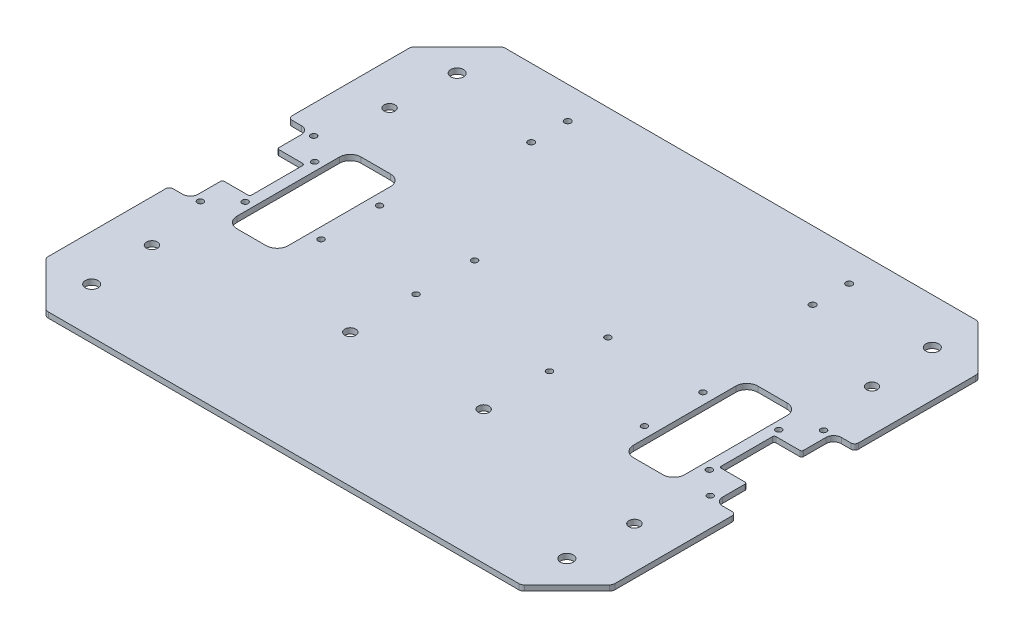
SolidWorks part; units mm, degrees
ref_plane "Plan de face" through (0, 0, 0) normal (0, 0, 1) x (1, 0, 0)
ref_plane "Plan de dessus" through (0, 0, 0) normal (0, 1, 0) x (1, 0, 0)
ref_plane "Plan de droite" through (0, 0, 0) normal (1, 0, 0) x (0, 0, -1)
sketch "Esquisse1" plane through (0, 0, 0) normal (0, 1, 0) x (1, 0, 0)
  line L0 (0, 125) -> (0, -125) construction
  line L1 (-155, 0) -> (155, 0) construction
  line L2 (-130, 125) -> (130, 125)
  line L3 (-130, -125) -> (130, -125)
  line L4 (-155, 100) -> (-155, -100)
  line L5 (155, 100) -> (155, -100)
  line L6 (-155, 100) -> (-130, 125)
  line L7 (-155, -100) -> (-130, -125)
  line L8 (130, -125) -> (155, -100)
  line L9 (130, 125) -> (155, 100)
  point P4 (0, 0)
  point P8 (0, 0)
  point P10 (0, 125)
  point P14 (0, -125)
  point P17 (-155, 0)
  point P20 (155, 0)
  dimension "D1" = 310
  dimension "D2" = 250
  dimension "D3" = 135
  dimension "D4" = 260
  dimension "D5" = 200
extrude "Boss.-Extru.1" add sketch "Esquisse1" along normal blind 3
fillet "Congé1" radius 3 8 edges at (-155, 1.5, 100) (-130, 1.5, 125) (130, 1.5, 125) (155, 1.5, 100) (155, 1.5, -100) (130, 1.5, -125) (-130, 1.5, -125) (-155, 1.5, -100)
sketch "Esquisse2" plane through (0, 3, 0) normal (0, 1, 0) x (1, 0, 0)
  line L0 (155, 0) -> (-155, 0) construction
  line L1 (-155, 98.7574) -> (-155, -98.7574) construction
  line L2 (-132, 0) -> (-132, -65) construction
  line L3 (-132, -65) -> (-155, -65) construction
  line L4 (0, 125) -> (0, -125) construction
  line L5 (-128.7574, -125) -> (128.7574, -125) construction
  circle A0 centre (-132, -65) radius 3
  circle A1 centre (-132, 65) radius 3
  circle A2 centre (132, -65) radius 3
  circle A3 centre (132, 65) radius 3
  point P6 (0, 0)
  point P18 (0, 0)
  dimension "D3" = 6
  dimension "D1" = 23
  dimension "D2" = 65
extrude "Perçage Profilé" cut sketch "Esquisse2" against normal through all
sketch "Esquisse3" plane through (0, 3, 0) normal (0, 1, 0) x (1, 0, 0)
  line L0 (-127, 19) -> (-127, -19) construction
  line L1 (155, 0) -> (-155, 0) construction
  line L2 (-155, 98.7574) -> (-155, -98.7574) construction
  line L3 (0, 125) -> (0, -125) construction
  line L4 (-128.7574, -125) -> (128.7574, -125) construction
  line L5 (-139.5, -31) -> (-139.5, 31) construction
  circle A0 centre (-127, 19) radius 1.65
  circle A1 centre (-127, -19) radius 1.65
  circle A2 centre (127, -19) radius 1.65
  circle A3 centre (127, 19) radius 1.65
  circle A4 centre (-139.5, 31) radius 1.65
  circle A5 centre (-139.5, -31) radius 1.65
  circle A6 centre (139.5, -31) radius 1.65
  circle A7 centre (139.5, 31) radius 1.65
  point P4 (-127, 0)
  point P10 (0, 0)
  point P16 (0, 0)
  point P23 (-139.5, 0)
  dimension "D2" = 3.3
  dimension "D1" = 38
  dimension "D3" = 28
  dimension "D4" = 62
  dimension "D5" = 12.5
extrude "Perçage Encodeur" cut sketch "Esquisse3" against normal through all
sketch "Esquisse4" plane through (0, 3, 0) normal (0, 1, 0) x (1, 0, 0)
  line L0 (155, 0) -> (-155, 0) construction
  line L1 (143.5, -15) -> (129.5, -15)
  line L2 (-128.5, -14) -> (-128.5, 14)
  line L4 (-129.5, 15) -> (-143.5, 15)
  line L5 (-143.5, 15) -> (-143.5, 32.5)
  line L6 (-143.5, 32.5) -> (-152, 32.5)
  line L7 (-152, 32.5) -> (-152, -32.5)
  line L8 (-152, -32.5) -> (-143.5, -32.5)
  line L9 (-143.5, -32.5) -> (-143.5, -15)
  line L10 (-143.5, -15) -> (-129.5, -15)
  line L12 (-143.5, 15) -> (-143.5, -15) construction
  line L13 (143.5, -32.5) -> (143.5, -15)
  line L14 (0, 125) -> (0, -125) construction
  line L15 (-128.7574, -125) -> (128.7574, -125) construction
  line L16 (152, -32.5) -> (143.5, -32.5)
  line L27 (-155, 98.7574) -> (-155, -98.7574) construction
  line L28 (152, 32.5) -> (152, -32.5)
  line L29 (143.5, 32.5) -> (152, 32.5)
  line L30 (143.5, 15) -> (143.5, 32.5)
  line L31 (129.5, 15) -> (143.5, 15)
  line L32 (128.5, -14) -> (128.5, 14)
  arc A0 (-128.5, -14) -> (-129.5, -15) centre (-129.5, -14) cw
  arc A1 (-128.5, 14) -> (-129.5, 15) centre (-129.5, 14) ccw
  arc A2 (128.5, 14) -> (129.5, 15) centre (129.5, 14) cw
  arc A3 (128.5, -14) -> (129.5, -15) centre (129.5, -14) ccw
  point P6 (0, 0)
  point P10 (-128.5, 0)
  point P19 (-143.5, 0)
  point P25 (0, 0)
  point P28 (-128.5, 15)
  point P32 (-152, 0)
  point P45 (128.5, 15)
  point P46 (128.5, 0)
  dimension "D2" = 1
  dimension "D1" = 15
  dimension "D3" = 8.5
  dimension "D4" = 65
  dimension "D5" = 30
  dimension "D6" = 3
extrude "Poche Roue Encodeuse" cut sketch "Esquisse4" against normal through all
fillet "Congé4" radius 1 4 edges at (143.5, 1.5, 15) (143.5, 1.5, -15) (-143.5, 1.5, 15) (-143.5, 1.5, -15)
fillet "Congé2" radius 4.25 4 edges at (152, 1.5, 32.5) (152, 1.5, -32.5) (-152, 1.5, 32.5) (-152, 1.5, -32.5)
fillet "Congé3" radius 4.25 4 edges at (143.5, 1.5, 32.5) (143.5, 1.5, -32.5) (-143.5, 1.5, 32.5) (-143.5, 1.5, -32.5)
sketch "Esquisse5" plane through (0, 3, 0) normal (0, 1, 0) x (1, 0, 0)
  line L0 (0, 125) -> (0, -125) construction
  line L1 (128.7574, 125) -> (-128.7574, 125) construction
  line L2 (-128.7574, -125) -> (128.7574, -125) construction
  line L3 (-155, 0) -> (155, 0) construction
  line L4 (-155, 98.7574) -> (-155, -98.7574) construction
  line L5 (155, -98.7574) -> (155, 98.7574) construction
  line L7 (-36.5, 16) -> (-88.5, 16) construction
  line L8 (-36.5, 16) -> (-36.5, -16) construction
  line L9 (-36.5, -16) -> (-88.5, -16) construction
  line L10 (-88.5, 16) -> (-88.5, -16) construction
  circle A0 centre (-88.5, 16) radius 1.65
  circle A1 centre (-88.5, -16) radius 1.65
  circle A2 centre (-36.5, -16) radius 1.65
  circle A3 centre (-36.5, 16) radius 1.65
  circle A4 centre (36.5, 16) radius 1.65
  circle A5 centre (36.5, -16) radius 1.65
  circle A6 centre (88.5, -16) radius 1.65
  circle A7 centre (88.5, 16) radius 1.65
  point P16 (-36.5, 0)
  dimension "D4" = 3.3
  dimension "D1" = 32
  dimension "D2" = 52
  dimension "D3" = 88.5
extrude "Perçage Bloc Moteur" cut sketch "Esquisse5" against normal through all
sketch "Esquisse6" plane through (0, 3, 0) normal (0, 1, 0) x (1, 0, 0)
  line L0 (-88.5, 16) -> (-88.5, -16) construction
  line L1 (-122.5, 34) -> (-94.5, 34)
  line L2 (-122.5, 34) -> (-122.5, -34)
  line L3 (-122.5, -34) -> (-94.5, -34)
  line L4 (-94.5, 34) -> (-94.5, -34)
  line L5 (-94.5, 0) -> (-88.5, 0) construction
  line L6 (0, 125) -> (0, -125) construction
  line L7 (-128.7574, -125) -> (128.7574, -125) construction
  line L8 (122.5, -34) -> (94.5, -34)
  line L9 (94.5, 34) -> (94.5, -34)
  line L10 (122.5, 34) -> (122.5, -34)
  line L11 (122.5, 34) -> (94.5, 34)
  point P16 (0, 0)
  dimension "D1" = 28
  dimension "D2" = 6
  dimension "D3" = 68
extrude "Poche Roue Motrice" cut sketch "Esquisse6" against normal through all
sketch "Esquisse7" plane through (0, 3, 0) normal (0, 1, 0) x (1, 0, 0)
  line L0 (-155, 98.7574) -> (-155, -98.7574) construction
  line L1 (128.7574, 125) -> (-128.7574, 125) construction
  line L2 (0, 125) -> (0, -125) construction
  line L3 (-128.7574, -125) -> (128.7574, -125) construction
  line L4 (-155, 0) -> (155, 0) construction
  line L5 (155, -98.7574) -> (155, 98.7574) construction
  circle A0 centre (-130, 100) radius 3.5
  circle A1 centre (-130, -100) radius 3.5
  circle A2 centre (130, -100) radius 3.5
  circle A3 centre (130, 100) radius 3.5
  point P12 (0, 0)
  point P18 (0, 0)
  dimension "D1" = 7
  dimension "D2" = 25
  dimension "D3" = 25
extrude "Perçage Patin" cut sketch "Esquisse7" against normal through all
sketch "Esquisse8" plane through (0, 3, 0) normal (0, 1, 0) x (1, 0, 0)
  line L0 (0, -125) -> (0, -52) construction
  line L1 (-128.7574, -125) -> (128.7574, -125) construction
  line L2 (36.5, -52) -> (-36.5, -52) construction
  circle A0 centre (-36.5, -52) radius 3
  circle A1 centre (36.5, -52) radius 3
  point P8 (0, -52)
  dimension "D3" = 6
  dimension "D1" = 73
  dimension "D2" = 73
extrude "Enlèv. mat.-Extru.1" cut sketch "Esquisse8" against normal through all
fillet "Congé5" radius 6 8 edges at (94.5, 1.5, 34) (122.5, 1.5, 34) (122.5, 1.5, -34) (94.5, 1.5, -34) (-122.5, 1.5, 34) (-94.5, 1.5, 34) (-94.5, 1.5, -34) (-122.5, 1.5, -34)
sketch "Esquisse9" plane through (0, 3, 0) normal (0, 1, 0) x (1, 0, 0)
  line L0 (-147.75, 32.5) -> (-155, 32.5)
  line L1 (-155, 98.7574) -> (-155, -98.7574) construction
  line L2 (-155, 32.5) -> (-155, -32.5)
  line L3 (-155, -32.5) -> (-147.75, -32.5)
  line L4 (-147.75, 32.5) -> (-147.75, -32.5)
  line L5 (0, 0) -> (0, -125) construction
  line L6 (-128.7574, -125) -> (128.7574, -125) construction
  line L7 (147.75, 32.5) -> (155, 32.5)
  line L8 (155, 32.5) -> (155, -32.5)
  line L9 (155, -32.5) -> (147.75, -32.5)
  line L10 (147.75, 32.5) -> (147.75, -32.5)
extrude "Enlèv. mat.-Extru.2" cut sketch "Esquisse9" against normal up to next
fillet "Congé6" radius 2 4 edges at (155, 1.5, 32.5) (155, 1.5, -32.5) (-155, 1.5, 32.5) (-155, 1.5, -32.5)
sketch "Esquisse10" plane through (0, 3, 0) normal (0, 1, 0) x (1, 0, 0)
  line L0 (0, 0) -> (0, 125) construction
  line L1 (128.7574, 125) -> (-128.7574, 125) construction
  line L2 (77, 107.5) -> (77, 87.5) construction
  circle A0 centre (77, 107.5) radius 1.75
  circle A1 centre (77, 87.5) radius 1.75
  circle A2 centre (-77, 87.5) radius 1.75
  circle A3 centre (-77, 107.5) radius 1.75
  dimension "D1" = 3.5
  dimension "D2" = 20
  dimension "D3" = 17.5
  dimension "D4" = 77
extrude "Enlèv. mat.-Extru.3" cut sketch "Esquisse10" against normal through all
